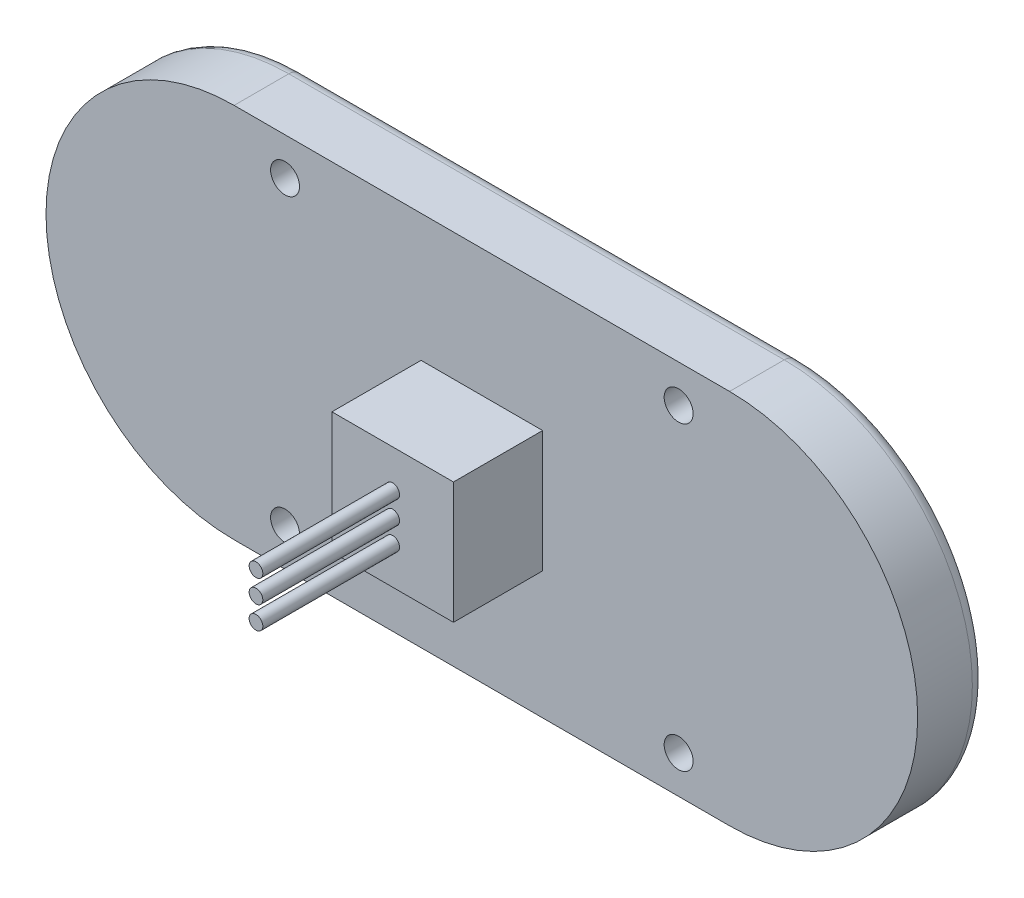
SolidWorks part; units mm, degrees
ref_plane "Front Plane" through (0, 0, 0) normal (0, 0, 1) x (1, 0, 0)
ref_plane "Top Plane" through (0, 0, 0) normal (0, 1, 0) x (1, 0, 0)
ref_plane "Right Plane" through (0, 0, 0) normal (1, 0, 0) x (0, 0, -1)
sketch "Sketch1" plane through (0, 0, 0) normal (0, 0, 1) x (1, 0, 0)
  line L0 (-43.18, 33.02) -> (43.18, -33.02) construction
  line L1 (-95.631, 41.275) -> (95.631, 41.275)
  line L2 (-95.631, 41.275) -> (-95.631, -41.275)
  line L3 (-95.631, -41.275) -> (95.631, -41.275)
  line L4 (95.631, 41.275) -> (95.631, -41.275)
  line L5 (-95.631, 41.275) -> (95.631, -41.275) construction
  line L6 (-95.631, -41.275) -> (95.631, 41.275) construction
  circle A0 centre (-43.18, 33.02) radius 3.175
  circle A1 centre (43.18, 33.02) radius 3.175
  circle A2 centre (-43.18, -33.02) radius 3.175
  circle A3 centre (43.18, -33.02) radius 3.175
  point P0 (0, 0)
  dimension "D3" = 6.35
  dimension "D1" = 191.262
  dimension "D2" = 82.55
  dimension "D4" = 86.36
  dimension "D5" = 66.04
extrude "Boss-Extrude1" add sketch "Sketch1" along normal blind 5
fillet "Fillet1" radius 41.275 4 edges at (-95.631, 41.275, 2.5) (95.631, 41.275, 2.5) (95.631, -41.275, 2.5) (-95.631, -41.275, 2.5)
sketch "Sketch2" plane through (0, 0, 5) normal (0, 0, 1) x (1, 0, 0)
  line L1 (-13.335, 13.335) -> (13.335, 13.335)
  line L2 (-13.335, 13.335) -> (-13.335, -13.335)
  line L3 (-13.335, -13.335) -> (13.335, -13.335)
  line L4 (13.335, 13.335) -> (13.335, -13.335)
  line L5 (-13.335, 13.335) -> (13.335, -13.335) construction
  line L6 (-13.335, -13.335) -> (13.335, 13.335) construction
  point P0 (0, 0)
  dimension "D1" = 26.67
  dimension "D2" = 26.67
extrude "Boss-Extrude2" add sketch "Sketch2" along normal blind 19.558
sketch "Sketch3" plane through (0, 0, 24.558) normal (0, 0, 1) x (1, 0, 0)
  circle A0 centre (0, 5) radius 1.5
  circle A1 centre (0, 0) radius 1.5
  circle A2 centre (0, -5) radius 1.5
  dimension "D1" = 3
  dimension "D2" = 5
  dimension "D3" = 5
extrude "Boss-Extrude3" add sketch "Sketch3" along normal blind 30
sketch "Sketch4" plane through (0, 0, 0) normal (0, 0, -1) x (-1, 0, 0)
  line L0 (-54.356, 41.275) -> (54.356, 41.275)
  line L1 (-54.356, -41.275) -> (54.356, -41.275)
  arc A0 (-54.356, 41.275) -> (-54.356, -41.275) centre (-54.356, 0) ccw
  arc A1 (54.356, 41.275) -> (54.356, -41.275) centre (54.356, 0) cw
  arc A2 (-54.356, 41.275) -> (-95.631, 0) centre (-54.356, 0) ccw construction
  arc A3 (95.631, 0) -> (54.356, 41.275) centre (54.356, 0) ccw construction
  circle A4 centre (-43.18, 33.02) radius 3.175
  circle A5 centre (43.18, 33.02) radius 3.175
  circle A6 centre (43.18, -33.02) radius 3.175
  circle A7 centre (-43.18, -33.02) radius 3.175
  dimension "D1" = 6.35
extrude "Boss-Extrude4" add sketch "Sketch4" along normal blind 10
fillet "Fillet2" radius 3 4 edges at (95.631, 0, -10) (0, -41.275, -10) (-95.631, 0, -10) (0, 41.275, -10)
sketch "Sketch5" plane through (0, 0, -10) normal (0, 0, -1) x (-1, 0, 0)
  line L0 (-54.356, 25) -> (54.356, 25)
  line L1 (-54.356, -25) -> (54.356, -25)
  line L2 (-54.356, -38.275) -> (-54.356, 38.275) construction
  arc A0 (-54.356, 25) -> (-54.356, -25) centre (-54.356, 0) ccw
  arc A1 (54.356, -25) -> (54.356, 25) centre (54.356, 0) ccw
  dimension "D1" = 50
extrude "Boss-Extrude5" add sketch "Sketch5" along normal blind 10
fillet "Fillet3" radius 10 4 edges at (79.356, 0, -20) (0, -25, -20) (-79.356, 0, -20) (0, 25, -20)
